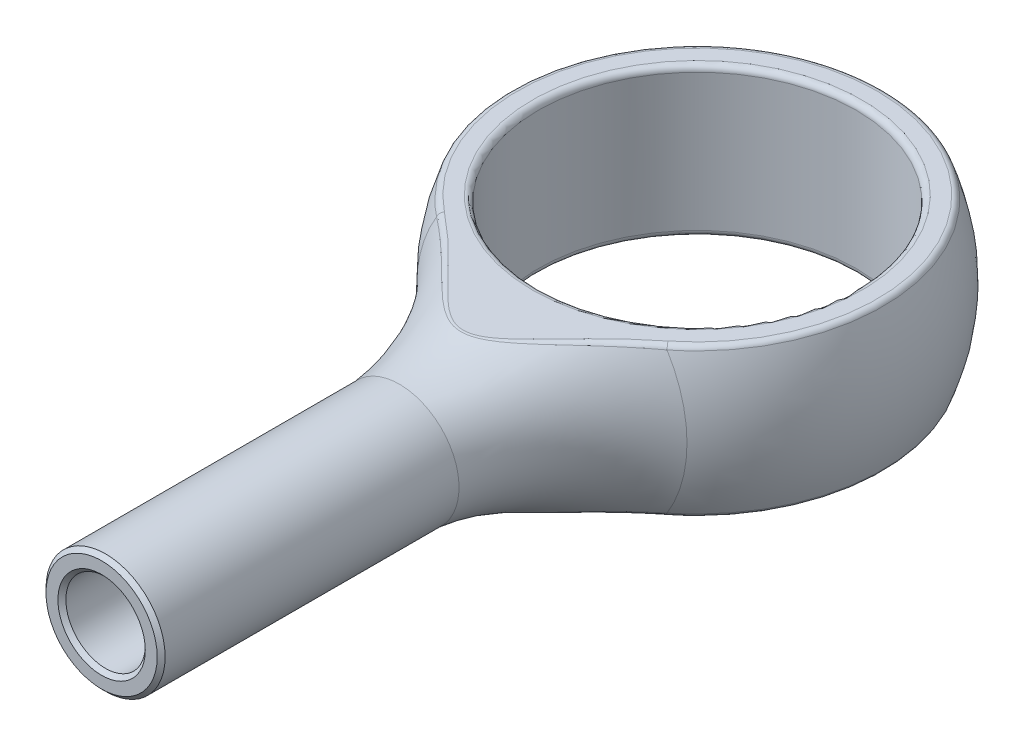
SolidWorks part; units mm, degrees
ref_plane "Front Plane" through (0, 0, 0) normal (0, 0, 1) x (1, 0, 0)
ref_plane "Top Plane" through (0, 0, 0) normal (0, 1, 0) x (1, 0, 0)
ref_plane "Right Plane" through (0, 0, 0) normal (1, 0, 0) x (0, 0, -1)
sketch "Sketch1" plane through (0, 0, 0) normal (0, 1, 0) x (1, 0, 0)
  line L0 (-1.5, -15) -> (1.5, -15)
  line L1 (1.5, -15) -> (1.5, -7.5)
  line L2 (-1.5, -15) -> (-1.5, -7.5)
  circle A0 centre (0, 0) radius 4
  circle A1 centre (0, 0) radius 5
  circle A2 centre (0, 0) radius 2 construction
  arc A3 (-1.5, -7.5) -> (-3.4036, -3.6627) centre (-7.5256, -8.0984) ccw
  arc A4 (1.5, -7.5) -> (3.3535, -3.7086) centre (7.16, -7.9183) cw
  point P7 (0, -15)
  point P14 (0, 0)
  point P15 (0, 0)
  point P16 (-3.8766, -3.1109)
  dimension "D1" = 10
  dimension "D2" = 8
  dimension "D3" = 4
  dimension "D4" = 3
  dimension "D5" = 15
  dimension "D6" = 7.5
sketch "Sketch2" plane through (0, 0, 0) normal (0, 1, 0) x (1, 0, 0)
  line L0 (-1.5, -15) -> (1.5, -15) construction
  line L1 (-1.5, -15) -> (-1.5, -7.5) construction
  line L2 (-1.5, -15) -> (0, -15)
  line L3 (-1.5, -15) -> (-1.5, -7.5)
  line L4 (0, 5) -> (0, -15)
  arc A0 (-1.5, -7.5) -> (-3.4036, -3.6627) centre (-7.5256, -8.0984) ccw construction
  circle A1 centre (0, 0) radius 5 construction
  arc A2 (-1.5, -7.5) -> (-3.4036, -3.6627) centre (-7.5256, -8.0984) ccw
  arc A3 (0, 5) -> (-3.4036, -3.6627) centre (0, 0) ccw
  point P2 (0, 0)
revolve "Revolve1" add sketch "Sketch2" angle 360 about L4
sketch "Sketch3" plane through (0, 0, 0) normal (1, 0, 0) x (0, 0, -1)
  line L0 (-28.5512, 11.4771) -> (8.2744, 11.4771)
  line L1 (8.2744, 11.4771) -> (8.2744, 1.875)
  line L2 (8.2744, 1.875) -> (-13.2615, 1.875)
  line L3 (-16.1293, 2.7792) -> (-28.5512, 11.4771)
  line L4 (0, 0) -> (11.8597, 0) construction
  line L5 (-16.1293, -2.7792) -> (-28.5512, -11.4771)
  line L6 (8.2744, -1.875) -> (-13.2615, -1.875)
  line L7 (8.2744, -11.4771) -> (8.2744, -1.875)
  line L8 (-28.5512, -11.4771) -> (8.2744, -11.4771)
  arc A0 (-13.2615, 1.875) -> (-16.1293, 2.7792) centre (-13.2615, 6.875) cw
  arc A1 (-13.2615, -1.875) -> (-16.1293, -2.7792) centre (-13.2615, -6.875) ccw
  point P15 (-22.0533, 10.5717)
  point P16 (-28.5512, 11.4771)
  dimension "D1" = 5
  dimension "D2" = 145
  dimension "D3" = 3.75
extrude "Cut-Extrude1" cut sketch "Sketch3" against normal blind 10 and the other way blind 10
sketch "Sketch4" plane through (0, 0, 0) normal (0, 1, 0) x (1, 0, 0)
  circle A0 centre (0, 0) radius 4 construction
  circle A1 centre (0, 0) radius 4
extrude "Cut-Extrude2" cut sketch "Sketch4" against normal blind 10 and the other way blind 10
fillet "Fillet1" radius 0.15 6 edges at (0, -1.875, -4) (0, -1.875, -4.6351) (0, 1.875, -4.6351) (-0.0981, -1.875, 5.9153) (0.0981, 1.875, 5.9153) (0, 1.875, 4)
sketch "Sketch5" plane through (0, 0, 15) normal (0, 0, 1) x (1, 0, 0)
  circle A0 centre (0, 0) radius 1
  dimension "D1" = 2
extrude "Cut-Extrude3" cut sketch "Sketch5" against normal blind 5
chamfer "Chamfer1" distance 0.1 angle 45 2 edges at (-1.5, 0, 15) (1, 0, 15)
